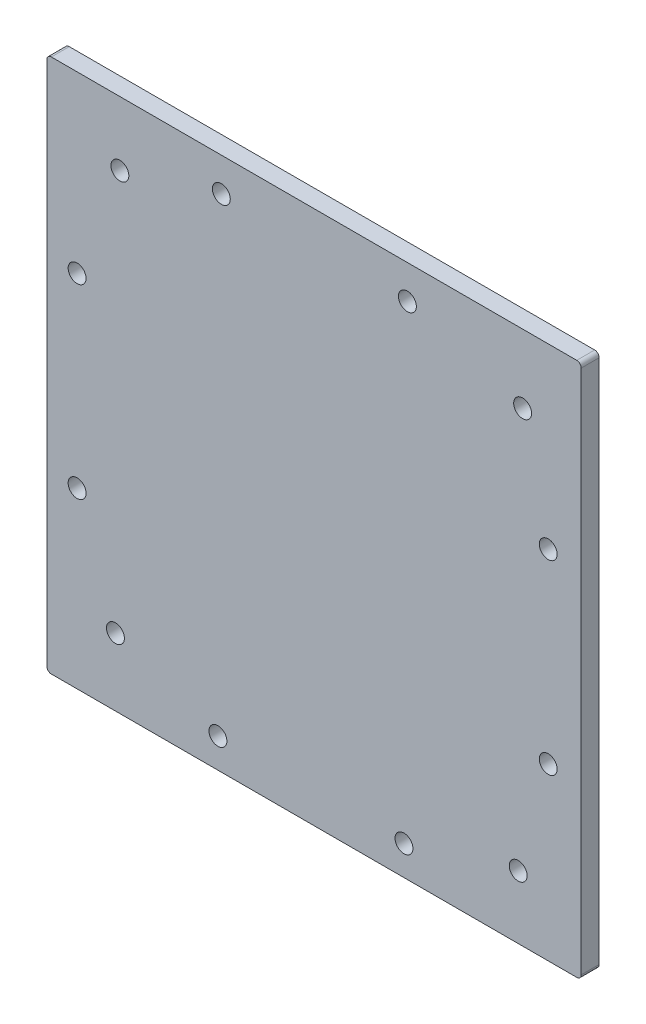
SolidWorks part; units mm, degrees
material "Acrylic (Medium-high impact)"
ref_plane "Front Plane" through (0, 0, 0) normal (0, 0, 1) x (1, 0, 0)
ref_plane "Top Plane" through (0, 0, 0) normal (0, 1, 0) x (1, 0, 0)
ref_plane "Right Plane" through (0, 0, 0) normal (1, 0, 0) x (0, 0, -1)
sketch "Sketch1" plane through (0, 0, 0) normal (0, 0, 1) x (1, 0, 0)
  line L1 (46.5772, -47.371) -> (-46.5773, -47.371)
  line L2 (47.371, -46.5773) -> (47.371, 46.5772)
  line L3 (46.5772, 47.371) -> (-46.5773, 47.371)
  line L4 (-47.371, -46.5773) -> (-47.371, 46.5772)
  line L5 (47.371, -47.371) -> (-47.371, 47.371) construction
  line L6 (47.371, 47.371) -> (-47.371, -47.371) construction
  arc A1 (-47.371, 46.5772) -> (-46.5773, 47.371) centre (-46.5773, 46.5772) cw
  arc A2 (46.5772, 47.371) -> (47.371, 46.5772) centre (46.5772, 46.5772) cw
  arc A3 (47.371, -46.5773) -> (46.5772, -47.371) centre (46.5772, -46.5773) cw
  arc A4 (-46.5773, -47.371) -> (-47.371, -46.5773) centre (-46.5773, -46.5773) cw
  point P2 (0, 0)
  dimension "D1" = 0.7937
  dimension "D2" = 94.742
extrude "Boss-Extrude1" add sketch "Sketch1" along normal blind 3.175
sketch "Sketch3" plane through (0, 0, 3.175) normal (0, 0, 1) x (1, 0, 0)
  circle A0 centre (15.9453, -42.1149) radius 1.5875 construction
  circle A1 centre (36.1931, -36.1931) radius 1.5875 construction
  circle A2 centre (41.5144, -17.1464) radius 1.5875 construction
  circle A3 centre (41.5144, 15.8381) radius 1.5875 construction
  circle A4 centre (36.9796, 35.2094) radius 1.5875 construction
  circle A5 centre (16.5459, 41.4071) radius 1.5875 construction
  circle A6 centre (-16.4386, 41.4071) radius 1.5875 construction
  circle A7 centre (-34.4229, 35.9959) radius 1.5875 construction
  circle A8 centre (-42.0077, 16.4386) radius 1.5875 construction
  circle A9 centre (-42.0077, -16.5459) radius 1.5875 construction
  circle A10 centre (-17.0392, -42.1149) radius 1.5875 construction
  circle A11 centre (-35.2094, -35.4065) radius 1.5875 construction
  circle A12 centre (15.9453, -42.1149) radius 1.5875
  circle A13 centre (36.1931, -36.1931) radius 1.5875
  circle A14 centre (41.5144, -17.1464) radius 1.5875
  circle A15 centre (41.5144, 15.8381) radius 1.5875
  circle A16 centre (36.9796, 35.2094) radius 1.5875
  circle A17 centre (16.5459, 41.4071) radius 1.5875
  circle A18 centre (-16.4386, 41.4071) radius 1.5875
  circle A19 centre (-34.4229, 35.9959) radius 1.5875
  circle A20 centre (-42.0077, 16.4386) radius 1.5875
  circle A21 centre (-42.0077, -16.5459) radius 1.5875
  circle A22 centre (-17.0392, -42.1149) radius 1.5875
  circle A23 centre (-35.2094, -35.4065) radius 1.5875
extrude "Cut-Extrude2" cut sketch "Sketch3" against normal up to next
